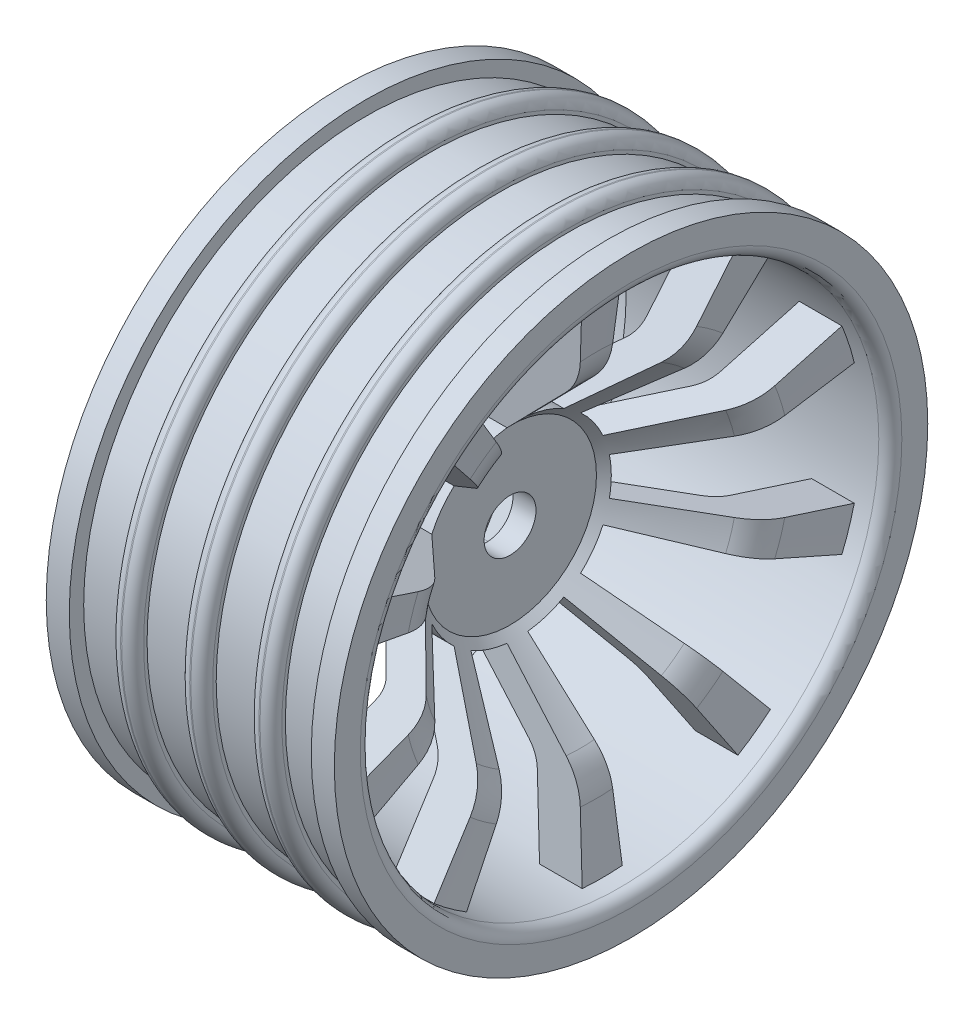
SolidWorks part; units mm, degrees
ref_plane "前视基准面" through (0, 0, 0) normal (0, 0, 1) x (1, 0, 0)
ref_plane "上视基准面" through (0, 0, 0) normal (0, 1, 0) x (1, 0, 0)
ref_plane "右视基准面" through (0, 0, 0) normal (1, 0, 0) x (0, 0, -1)
other "Configuration Table"
sketch "Rim and Hub Cross Section" plane through (0, 0, 0) normal (0, 0, 1) x (1, 0, 0)
  line L0 (0, 0) -> (0, 24.5) construction
  line L1 (-5, 24.5) -> (-1, 24.5)
  line L2 (-5, 24.5) -> (-5, 24.8)
  line L3 (-5.95, 25.75) -> (-6.05, 25.75)
  line L4 (-7, 24.8) -> (-7, 24.5)
  line L5 (-7, 24.5) -> (-10.5, 24.5)
  line L6 (-10.5, 24.5) -> (-10.5, 25.75)
  line L7 (-10.5, 25.75) -> (-12.5, 25.75)
  line L8 (-12.5, 25.75) -> (-12.5, 23.7)
  line L9 (-10.4215, 22.5) -> (6.3, 22.5)
  line L10 (-1, 24.5) -> (-1, 24.8)
  line L11 (-0.05, 25.75) -> (0.05, 25.75)
  line L12 (1, 24.5) -> (1, 24.8)
  line L13 (12.5, 25.75) -> (12.5, 23.5)
  line L14 (10.5, 25.75) -> (12.5, 25.75)
  line L15 (10.5, 24.5) -> (10.5, 25.75)
  line L16 (7, 24.5) -> (10.5, 24.5)
  line L17 (7, 24.8) -> (7, 24.5)
  line L18 (5.95, 25.75) -> (6.05, 25.75)
  line L19 (5, 24.5) -> (5, 24.8)
  line L20 (5, 24.5) -> (1, 24.5)
  line L21 (-12.5, 23.7) -> (-10.4215, 22.5)
  line L22 (0, 0) -> (-29.6095, 0) construction
  line L23 (10, 22.5) -> (9.4999, 16.7833)
  line L24 (8.0914, 13.7209) -> (2, 7.5)
  line L25 (2, 7.5) -> (2, 2.25)
  line L26 (6.3, 22.5) -> (5.7148, 15.8107)
  line L27 (4.8697, 13.9732) -> (0, 9)
  line L28 (0, 9) -> (0, 8)
  line L29 (0, 8) -> (-4, 8)
  line L30 (-4, 8) -> (-4, 2.25)
  line L31 (-4, 2.25) -> (2, 2.25)
  line L32 (10, 22.5) -> (11.5, 22.5)
  arc A0 (5.95, 25.75) -> (5, 24.8) centre (5.95, 24.8) ccw
  arc A1 (7, 24.8) -> (6.05, 25.75) centre (6.05, 24.8) ccw
  arc A2 (1, 24.8) -> (0.05, 25.75) centre (0.05, 24.8) ccw
  arc A3 (-6.05, 25.75) -> (-7, 24.8) centre (-6.05, 24.8) ccw
  arc A4 (-5, 24.8) -> (-5.95, 25.75) centre (-5.95, 24.8) ccw
  arc A5 (-1, 24.8) -> (-0.05, 25.75) centre (-0.05, 24.8) cw
  arc A6 (12.5, 23.5) -> (11.5, 22.5) centre (11.5, 23.5) cw
  arc A7 (9.4999, 16.7833) -> (8.0914, 13.7209) centre (4.5189, 17.2191) cw
  arc A8 (5.7148, 15.8107) -> (4.8697, 13.9732) centre (2.7262, 16.0721) cw
  point P11 (-12.5, 22.5)
  point P16 (0, 25.75)
  point P18 (0, 22.5)
  point P27 (5, 25.75)
  point P30 (7, 25.75)
  point P33 (1, 25.75)
  point P36 (-7, 25.75)
  point P39 (-5, 25.75)
  point P42 (-1, 25.75)
  point P47 (12.5, 22.5)
  point P61 (9.3438, 15)
  dimension "D8" = 0.95
  dimension "D11" = 1
  dimension "D23" = 5
  dimension "D24" = 3
  dimension "D1" = 12.5
  dimension "InnerBarrelRadius" = 22.5
  dimension "D3" = 25.75
  dimension "D4" = 24.5
  dimension "D5" = 2
  dimension "D6" = 3.5
  dimension "D7" = 2
  dimension "D9" = 1.2
  dimension "D10" = 60
  dimension "D12" = 2.5
  dimension "D13" = 18.8
  dimension "D14" = 8.5
  dimension "D15" = 8
  dimension "AxleBoreRadius" = 2.25
  dimension "D17" = 10.5
  dimension "D18" = 15
  dimension "D19" = 5
  dimension "D20" = 7.5
  dimension "D21" = 9
  dimension "D22" = 12.5
revolve "Rim and Hub Profile" add sketch "Rim and Hub Cross Section" angle 360 about L22
sketch "Rear Hex Socket Profile" plane through (-4, 0, 0) normal (-1, 0, 0) x (0, 0, 1)
  line L1 (-6.8416, -0.25) -> (-3.6373, -5.8)
  line L2 (-3.2043, -6.05) -> (3.2043, -6.05)
  line L3 (3.6373, -5.8) -> (6.8416, -0.25)
  line L4 (6.8416, 0.25) -> (3.6373, 5.8)
  line L5 (3.2043, 6.05) -> (-3.2043, 6.05)
  line L6 (-3.6373, 5.8) -> (-6.8416, 0.25)
  circle A0 centre (0, 0) radius 6.05 construction
  arc A1 (-3.2043, 6.05) -> (-3.6373, 5.8) centre (-3.2043, 5.55) ccw
  arc A2 (3.6373, 5.8) -> (3.2043, 6.05) centre (3.2043, 5.55) ccw
  arc A3 (6.8416, -0.25) -> (6.8416, 0.25) centre (6.4086, 0) ccw
  arc A4 (3.2043, -6.05) -> (3.6373, -5.8) centre (3.2043, -5.55) ccw
  arc A5 (-3.6373, -5.8) -> (-3.2043, -6.05) centre (-3.2043, -5.55) ccw
  arc A6 (-6.8416, -0.25) -> (-6.8416, 0.25) centre (-6.4086, 0) cw
  dimension "D2" = 0.5
  dimension "HexAcrossFlats" = 12.1
extrude "Rear Hex Socket" cut sketch "Rear Hex Socket Profile" against normal blind 4
sketch "草图3" plane through (12.5, 0, 0) normal (1, 0, 0) x (0, 0, -1)
  line L0 (0, 0) -> (0, 30.1635) construction
  line L1 (-0.75, 7.9648) -> (-4, 22.1416)
  line L2 (0.75, 7.9648) -> (4, 22.1416)
  line L3 (-0.75, 7.9648) -> (0.75, 7.9648) construction
  line L4 (3.3329, 7.2727) -> (7.6067, 21.1752)
  line L5 (4.6319, 6.5227) -> (14.5349, 17.1752)
  line L6 (6.5227, 4.6319) -> (17.1752, 14.5349)
  line L7 (7.2727, 3.3329) -> (21.1752, 7.6067)
  line L8 (7.9648, 0.75) -> (22.1416, 4)
  line L9 (7.9648, -0.75) -> (22.1416, -4)
  line L10 (7.2727, -3.3329) -> (21.1752, -7.6067)
  line L11 (6.5227, -4.6319) -> (17.1752, -14.5349)
  line L12 (4.6319, -6.5227) -> (14.5349, -17.1752)
  line L13 (3.3329, -7.2727) -> (7.6067, -21.1752)
  line L14 (0.75, -7.9648) -> (4, -22.1416)
  line L15 (-0.75, -7.9648) -> (-4, -22.1416)
  line L16 (-3.3329, -7.2727) -> (-7.6067, -21.1752)
  line L17 (-4.6319, -6.5227) -> (-14.5349, -17.1752)
  line L18 (-6.5227, -4.6319) -> (-17.1752, -14.5349)
  line L19 (-7.2727, -3.3329) -> (-21.1752, -7.6067)
  line L20 (-7.9648, -0.75) -> (-22.1416, -4)
  line L21 (-7.9648, 0.75) -> (-22.1416, 4)
  line L22 (-7.2727, 3.3329) -> (-21.1752, 7.6067)
  line L23 (-6.5227, 4.6319) -> (-17.1752, 14.5349)
  line L24 (-4.6319, 6.5227) -> (-14.5349, 17.1752)
  line L25 (-3.3329, 7.2727) -> (-7.6067, 21.1752)
  arc A0 (0.75, 7.9648) -> (-0.75, 7.9648) centre (0, 0) ccw
  arc A1 (14.5349, 17.1752) -> (7.6067, 21.1752) centre (0, 0) ccw
  circle A2 centre (0, 0) radius 22.5
  arc A3 (4, 22.1416) -> (-4, 22.1416) centre (0, 0) ccw
  arc A4 (4.6319, 6.5227) -> (3.3329, 7.2727) centre (0, 0) ccw
  arc A5 (21.1752, 7.6067) -> (17.1752, 14.5349) centre (0, 0) ccw
  arc A6 (7.2727, 3.3329) -> (6.5227, 4.6319) centre (0, 0) ccw
  arc A7 (22.1416, -4) -> (22.1416, 4) centre (0, 0) ccw
  arc A8 (7.9648, -0.75) -> (7.9648, 0.75) centre (0, 0) ccw
  arc A9 (17.1752, -14.5349) -> (21.1752, -7.6067) centre (0, 0) ccw
  arc A10 (6.5227, -4.6319) -> (7.2727, -3.3329) centre (0, 0) ccw
  arc A11 (7.6067, -21.1752) -> (14.5349, -17.1752) centre (0, 0) ccw
  arc A12 (3.3329, -7.2727) -> (4.6319, -6.5227) centre (0, 0) ccw
  arc A13 (-4, -22.1416) -> (4, -22.1416) centre (0, 0) ccw
  arc A14 (-0.75, -7.9648) -> (0.75, -7.9648) centre (0, 0) ccw
  arc A15 (-14.5349, -17.1752) -> (-7.6067, -21.1752) centre (0, 0) ccw
  arc A16 (-4.6319, -6.5227) -> (-3.3329, -7.2727) centre (0, 0) ccw
  arc A17 (-21.1752, -7.6067) -> (-17.1752, -14.5349) centre (0, 0) ccw
  arc A18 (-7.2727, -3.3329) -> (-6.5227, -4.6319) centre (0, 0) ccw
  arc A19 (-22.1416, 4) -> (-22.1416, -4) centre (0, 0) ccw
  arc A20 (-7.9648, 0.75) -> (-7.9648, -0.75) centre (0, 0) ccw
  arc A21 (-17.1752, 14.5349) -> (-21.1752, 7.6067) centre (0, 0) ccw
  arc A22 (-6.5227, 4.6319) -> (-7.2727, 3.3329) centre (0, 0) ccw
  arc A23 (-7.6067, 21.1752) -> (-14.5349, 17.1752) centre (0, 0) ccw
  arc A24 (-3.3329, 7.2727) -> (-4.6319, 6.5227) centre (0, 0) ccw
  point P54 (0, 0)
  dimension "D1" = 16
  dimension "D4" = 1.5
  dimension "D3" = 8
  dimension "D2" = 0
  dimension "D5" = 12
extrude "Legacy - Twelve Spoke Windows" [suppressed] cut sketch "草图3" against normal through all
sketch "草图4" [suppressed] plane through (2, 0, 0) normal (1, 0, 0) x (0, 0, -1)
  line L0 (-4.6319, 6.5227) -> (-4.1286, 5.9813)
  line L1 (-3.1157, 6.5661) -> (-3.3329, 7.2727)
  line L2 (-5.0224, 12.7687) -> (-3.3329, 7.2727) construction
  line L3 (-4.6319, 6.5227) -> (-8.5468, 10.7339) construction
  line L4 (-3.3329, 7.2727) -> (-3.8329, 8.1387)
  line L5 (-3.8329, 8.1387) -> (-5.1319, 7.3887)
  line L6 (-5.1319, 7.3887) -> (-4.6319, 6.5227)
  line L7 (-3.3892, 5.8702) -> (-4.4824, 7.7637) construction
  line L8 (0, 0) -> (0, 8) construction
  line L9 (-0.75, 7.9648) -> (-0.75, 8.9648)
  line L10 (-0.75, 8.9648) -> (0, 8.9648)
  line L11 (-6.5227, 4.6319) -> (-7.3887, 5.1319)
  line L12 (-7.3887, 5.1319) -> (-7.7637, 4.4824)
  line L13 (6.5227, 4.6319) -> (7.3887, 5.1319)
  line L14 (7.3887, 5.1319) -> (7.7637, 4.4824)
  line L15 (4.1286, 5.9813) -> (4.6319, 6.5227)
  line L16 (4.6319, 6.5227) -> (5.1319, 7.3887)
  line L17 (5.1319, 7.3887) -> (3.8329, 8.1387)
  line L18 (3.8329, 8.1387) -> (3.3329, 7.2727)
  line L19 (3.3329, 7.2727) -> (3.1157, 6.5661)
  line L20 (0.75, 7.9648) -> (0.75, 8.9648)
  line L21 (0.75, 8.9648) -> (0, 8.9648)
  line L22 (7.2727, -3.3329) -> (8.1387, -3.8329)
  line L23 (8.1387, -3.8329) -> (7.7637, -4.4824)
  line L24 (7.2443, -0.5848) -> (7.9648, -0.75)
  line L25 (7.9648, -0.75) -> (8.9648, -0.75)
  line L26 (8.9648, -0.75) -> (8.9648, 0.75)
  line L27 (8.9648, 0.75) -> (7.9648, 0.75)
  line L28 (7.9648, 0.75) -> (7.2443, 0.5848)
  line L29 (7.2727, 3.3329) -> (8.1387, 3.8329)
  line L30 (8.1387, 3.8329) -> (7.7637, 4.4824)
  line L31 (0.75, -7.9648) -> (0.75, -8.9648)
  line L32 (0.75, -8.9648) -> (0, -8.9648)
  line L33 (3.1157, -6.5661) -> (3.3329, -7.2727)
  line L34 (3.3329, -7.2727) -> (3.8329, -8.1387)
  line L35 (3.8329, -8.1387) -> (5.1319, -7.3887)
  line L36 (5.1319, -7.3887) -> (4.6319, -6.5227)
  line L37 (4.6319, -6.5227) -> (4.1286, -5.9813)
  line L38 (6.5227, -4.6319) -> (7.3887, -5.1319)
  line L39 (7.3887, -5.1319) -> (7.7637, -4.4824)
  line L40 (-6.5227, -4.6319) -> (-7.3887, -5.1319)
  line L41 (-7.3887, -5.1319) -> (-7.7637, -4.4824)
  line L42 (-4.1286, -5.9813) -> (-4.6319, -6.5227)
  line L43 (-4.6319, -6.5227) -> (-5.1319, -7.3887)
  line L44 (-5.1319, -7.3887) -> (-3.8329, -8.1387)
  line L45 (-3.8329, -8.1387) -> (-3.3329, -7.2727)
  line L46 (-3.3329, -7.2727) -> (-3.1157, -6.5661)
  line L47 (-0.75, -7.9648) -> (-0.75, -8.9648)
  line L48 (-0.75, -8.9648) -> (0, -8.9648)
  line L49 (-7.2727, 3.3329) -> (-8.1387, 3.8329)
  line L50 (-8.1387, 3.8329) -> (-7.7637, 4.4824)
  line L51 (-7.2443, 0.5848) -> (-7.9648, 0.75)
  line L52 (-7.9648, 0.75) -> (-8.9648, 0.75)
  line L53 (-8.9648, 0.75) -> (-8.9648, -0.75)
  line L54 (-8.9648, -0.75) -> (-7.9648, -0.75)
  line L55 (-7.9648, -0.75) -> (-7.2443, -0.5848)
  line L56 (-7.2727, -3.3329) -> (-8.1387, -3.8329)
  line L57 (-8.1387, -3.8329) -> (-7.7637, -4.4824)
  arc A0 (-4.1286, 5.9813) -> (-3.1157, 6.5661) centre (-3.6892, 6.3898) ccw
  circle A1 centre (0, 0) radius 5 construction
  arc A2 (-0.75, 7.9648) -> (-6.5227, 4.6319) centre (-4.2901, 7.4306) cw
  arc A3 (0.75, 7.9648) -> (-0.75, 7.9648) centre (0, 0) ccw construction
  arc A4 (6.5227, 4.6319) -> (0.75, 7.9648) centre (4.2901, 7.4306) cw
  arc A5 (3.1157, 6.5661) -> (4.1286, 5.9813) centre (3.6892, 6.3898) ccw
  arc A6 (7.2727, -3.3329) -> (7.2727, 3.3329) centre (8.5801, 0) cw
  arc A7 (7.2443, 0.5848) -> (7.2443, -0.5848) centre (7.3783, 0) ccw
  arc A8 (0.75, -7.9648) -> (6.5227, -4.6319) centre (4.2901, -7.4306) cw
  arc A9 (4.1286, -5.9813) -> (3.1157, -6.5661) centre (3.6892, -6.3898) ccw
  arc A10 (-6.5227, -4.6319) -> (-0.75, -7.9648) centre (-4.2901, -7.4306) cw
  arc A11 (-3.1157, -6.5661) -> (-4.1286, -5.9813) centre (-3.6892, -6.3898) ccw
  arc A12 (-7.2727, 3.3329) -> (-7.2727, -3.3329) centre (-8.5801, 0) cw
  arc A13 (-7.2443, -0.5848) -> (-7.2443, 0.5848) centre (-7.3783, 0) ccw
  point P104 (0, 0)
  dimension "D1" = 0.6
  dimension "D2" = 10
  dimension "D3" = 1
  dimension "D4" = 6
extrude "Legacy - Hub Scallops" [suppressed] cut sketch "草图4" along normal through all from offset 0.5 offset against normal yes
fillet "Legacy - 圆角1" [suppressed] radius 1
fillet "Legacy - 圆角2" [suppressed] radius 0.25
ref_axis "Axle Axis" through (-13.75, 0, 0) along (1, 0, 0)
sketch "Tapered Spoke Window Profile" plane through (0, 0, 0) normal (1, 0, 0) x (0, 0, -1)
  line L0 (7.9818, -1.6471) -> (21.8724, -5.2772)
  line L1 (21.8724, 5.2772) -> (7.9818, 1.6471)
  arc A0 (21.8724, -5.2772) -> (21.8724, 5.2772) centre (0, 0) ccw
  arc A1 (7.9818, 1.6471) -> (7.9818, -1.6471) centre (0, 0) cw
extrude "Spoke Window - Through Both Ways" cut sketch "Tapered Spoke Window Profile" against normal through all and the other way through all
pattern_circular "Circular Spoke Pattern" count 10 over 360 about axis through (-13.75, 0, 0) along (1, 0, 0) of "Spoke Window - Through Both Ways"
equation "\"AxleBore\"= 4.5mm"
equation "\"NominalDriveHex\"= 12mm"
equation "\"HexFitClearance\"= 0.1mm"
equation "\"AxleBoreRadius@Rim and Hub Cross Section\" = \"AxleBore\" / 2"
equation "\"HexAcrossFlats@Rear Hex Socket Profile\" = \"NominalDriveHex\" + \"HexFitClearance\""
